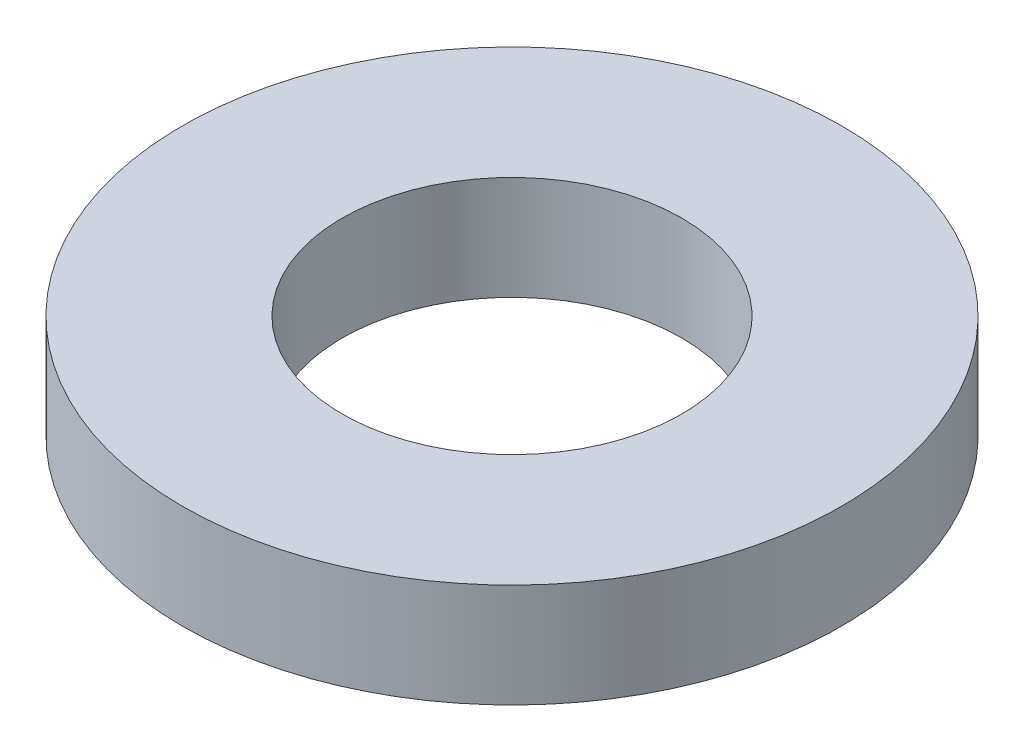
SolidWorks part; units mm, degrees
ref_plane "Front Plane" through (0, 0, 0) normal (0, 0, 1) x (1, 0, 0)
ref_plane "Top Plane" through (0, 0, 0) normal (0, 1, 0) x (1, 0, 0)
ref_plane "Right Plane" through (0, 0, 0) normal (1, 0, 0) x (0, 0, -1)
sketch "Sketch1" plane through (0, 0, 0) normal (0, 1, 0) x (1, 0, 0)
  circle A0 centre (0, 0) radius 82.5
  dimension "FLANGE_OD" = 165
extrude "Boss-Extrude1" add sketch "Sketch1" along normal blind 26
sketch "Sketch2" plane through (0, 0, 0) normal (0, 1, 0) x (1, 0, 0)
  circle A0 centre (0, 0) radius 42.5
  dimension "BORE_D" = 85
extrude "Cut-Extrude1" cut sketch "Sketch2" along normal through all
sketch "Sketch3" plane through (0, 26, 0) normal (0, 1, 0) x (1, 0, 0)
  circle A0 centre (0, 0) radius 29.6449 construction
  circle A1 centre (-29.6449, 0) radius 4.8739
  dimension "BOLT_D" = 9.7478
  dimension "BOLT_PCD" = 59.2898
extrude "Cut-Extrude2" cut sketch "Sketch3" against normal blind 24.8074 rebuild error yes
pattern_circular "CirPattern1" count 4 over 360 rebuild error yes
